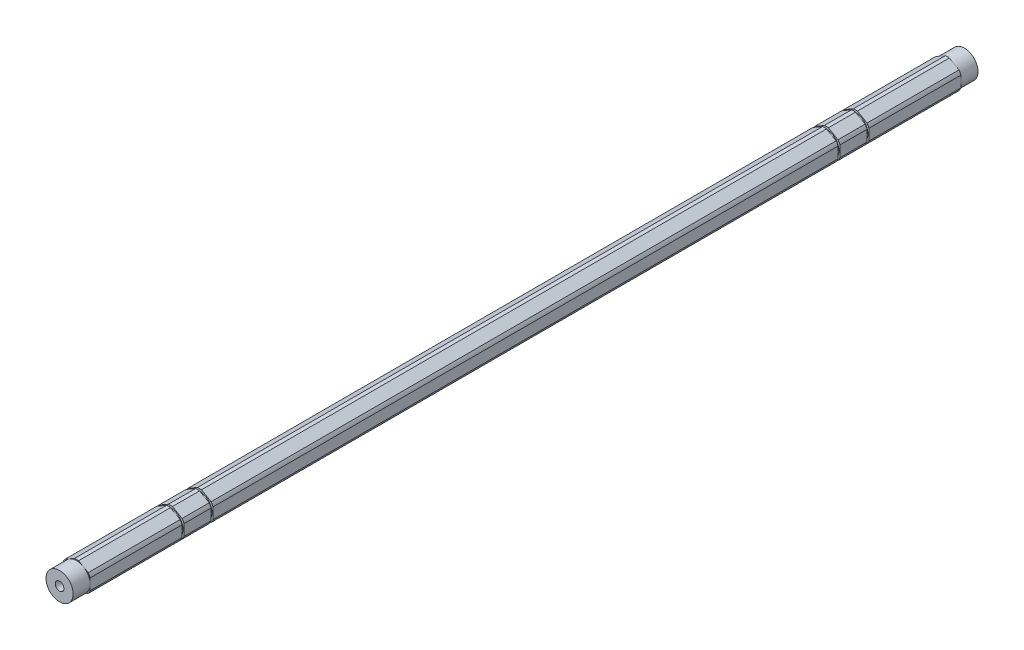
SolidWorks part; units mm, degrees
ref_plane "Front Plane" through (0, 0, 0) normal (0, 0, 1) x (1, 0, 0)
ref_plane "Top Plane" through (0, 0, 0) normal (0, 1, 0) x (1, 0, 0)
ref_plane "Right Plane" through (0, 0, 0) normal (1, 0, 0) x (0, 0, -1)
sketch "Sketch1" plane through (0, 0, 0) normal (0, 0, 1) x (1, 0, 0)
  line L1 (0, 7.3323) -> (-6.35, 3.6662)
  line L2 (-6.35, 3.6662) -> (-6.35, -3.6662)
  line L3 (-6.35, -3.6662) -> (0, -7.3323)
  line L4 (0, -7.3323) -> (6.35, -3.6662)
  line L5 (6.35, -3.6662) -> (6.35, 3.6662)
  line L6 (6.35, 3.6662) -> (0, 7.3323)
  circle A0 centre (0, 0) radius 6.35 construction
  circle A1 centre (0, 0) radius 6.858
  dimension "D1" = 12.7
  dimension "D2" = 13.716
extrude "Boss-Extrude1" add sketch "Sketch1" along normal mid plane 406.4 contours L5 A1 L6 L1 L2 L3 L4 region at (0, 0, 0)
sketch "Sketch6" plane through (0, 0, 203.2) normal (0, 0, 1) x (1, 0, 0)
  line L0 (5.4183, 4.2041) -> (0.9317, 6.7944) construction
  circle A0 centre (0, 0) radius 6.35
extrude "Boss-Extrude2" add sketch "Sketch6" along normal blind 7.9375
mirror "Mirror2" about plane through (0, 0, 0) normal (0, 0, 1) of "Boss-Extrude2"
hole_wizard "#10-32 Tapped Hole1" positions "3DSketch1" profile "Sketch2" tap size "#10-32" standard "ANSI Inch"
sketch3d "3DSketch1"
  line L0 (0, 0, 211.1375) -> (0, 0, 203.2) construction
  line L1 (0, 0, -211.1375) -> (0, 0, -203.2) construction
  point P11 (0, 0, 211.1375)
  point P15 (0, 0, -211.1375)
sketch "Sketch2" plane through (0, 0, 211.1375) normal (1, 0, 0) x (0, -1, 0)
  line L0 (0, 0) -> (0, 17.5608)
  line L1 (0, 17.5608) -> (2.0193, 16.3474)
  line L2 (2.0193, 16.3474) -> (2.0193, 0)
  line L5 (2.0193, 0) -> (0, 0)
  line L10 (0, 17.5608) -> (-2.0193, 16.3474) construction
  line L11 (0, -6.35) -> (0, 107.95) construction
  dimension "Tap Drill Dia." = 4.0386
  dimension "Tap Drill Depth" = 16.3474
  dimension "Drill Angle" = 118
cosmetic thread "Hole Thread1" parameters "D1"=13.97, "D2"=4.826
cosmetic thread "Hole Thread2" parameters "D1"=13.97, "D2"=4.826
sketch "Sketch5" plane through (0, 0, 0) normal (1, 0, 0) x (0, 0, -1)
  line L0 (203.2, 6.858) -> (-203.2, 6.858) construction
  line L1 (-160.2727, 6.858) -> (-159.3837, 6.858)
  line L2 (-160.2727, 6.858) -> (-160.2727, 5.8547)
  line L3 (-160.2727, 5.8547) -> (-159.3837, 5.8547)
  line L4 (-159.3837, 6.858) -> (-159.3837, 5.8547)
  line L5 (-165.0472, 0) -> (-158.8423, 0) construction
  line L6 (-146.7472, 6.858) -> (-145.8582, 6.858)
  line L7 (-146.7472, 6.858) -> (-146.7472, 5.8547)
  line L8 (-146.7472, 5.8547) -> (-145.8582, 5.8547)
  line L9 (-145.8582, 6.858) -> (-145.8582, 5.8547)
  line L10 (-159.3837, 6.858) -> (-146.7472, 6.858) construction
  line L11 (-203.2, 6.858) -> (-203.2, 6.7944) construction
  point P16 (-153.0655, 6.858)
  dimension "D1" = 5.8547
  dimension "D2" = 0.889
  dimension "D3" = 50.1345
  dimension "D4" = 12.6365
revolve "Cut-Revolve1" cut sketch "Sketch5" angle 360 about L5
mirror "Mirror1" about plane through (0, 0, 0) normal (0, 0, 1) of "Cut-Revolve1"
